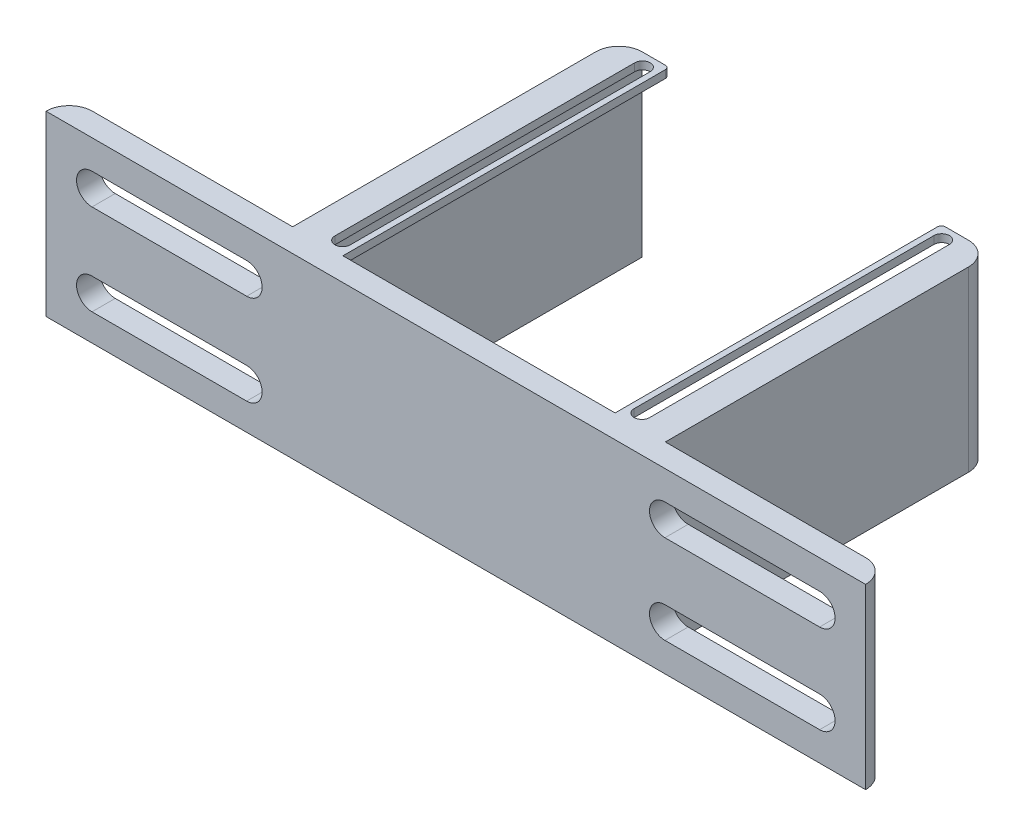
SolidWorks part; units mm, degrees
ref_plane "Front Plane" through (0, 0, 0) normal (0, 0, 1) x (1, 0, 0)
ref_plane "Top Plane" through (0, 0, 0) normal (0, 1, 0) x (1, 0, 0)
ref_plane "Right Plane" through (0, 0, 0) normal (1, 0, 0) x (0, 0, -1)
sketch "Sketch1" plane through (0, 0, 0) normal (0, 1, 0) x (1, 0, 0)
  line L0 (-53, 0) -> (53, 0)
  line L1 (53, 0) -> (53, 3)
  line L2 (53, 3) -> (24.1, 3)
  line L3 (24.1, 3) -> (24.1, 45.2)
  line L4 (24.1, 45.2) -> (21.1, 45.2)
  line L5 (21.1, 45.2) -> (21.1, 3)
  line L6 (21.1, 3) -> (-21.1, 3)
  line L7 (0, 0) -> (0, 100) construction
  line L9 (-53, 0) -> (-53, 3)
  line L10 (21.1, 3) -> (18.1, 3)
  line L11 (21.1, 3) -> (21.1, 45.2)
  line L12 (21.1, 45.2) -> (18.1, 45.2)
  line L13 (18.1, 3) -> (18.1, 45.2)
  line L14 (-53, 3) -> (-24.1, 3)
  line L15 (-24.1, 3) -> (-24.1, 45.2)
  line L16 (-24.1, 45.2) -> (-21.1, 45.2)
  line L17 (-21.1, 45.2) -> (-18.1, 45.2)
  line L18 (-21.1, 45.2) -> (-21.1, 3)
  line L19 (-18.1, 3) -> (-18.1, 45.2)
  point P20 (0, 3)
  dimension "D1" = 28.9
  dimension "D2" = 3
  dimension "D3" = 3
  dimension "D4" = 21.1
  dimension "D5" = 3
  dimension "D6" = 42.2
  dimension "D7" = 3
extrude "Boss-Extrude5" add sketch "Sketch1" along normal blind 23 contours L18 L6 L5 L4 L3 L2 L1 L0 L9 L14 L15 L16
sketch "Sketch3" plane through (0, 0, -3) normal (0, 0, -1) x (-1, 0, 0)
  line L1 (-21.1, 23) -> (-17.6, 23)
  line L2 (-21.1, 23) -> (-21.1, 22)
  line L3 (-21.1, 22) -> (-17.6, 22)
  line L4 (-17.6, 23) -> (-17.6, 22)
  line L5 (21.1, 23) -> (17.6, 23)
  line L6 (21.1, 23) -> (21.1, 22)
  line L7 (21.1, 22) -> (17.6, 22)
  line L8 (17.6, 23) -> (17.6, 22)
  point P10 (-17.6, 22.5)
  dimension "D1" = 1
  dimension "D2" = 3.5
  dimension "D3" = 1
  dimension "D4" = 3.5
extrude "Boss-Extrude7" add sketch "Sketch3" along normal blind 42.2
sketch "Sketch4" plane through (0, 23, 0) normal (0, 1, 0) x (1, 0, 0)
  line L0 (17.6, 45.2) -> (24.1, 45.2) construction
sketch "Sketch5" plane through (0, 22, 0) normal (0, -1, 0) x (-1, 0, 0)
  line L0 (19.35, 45.2) -> (19.35, 3) construction
  line L1 (17.6, 45.2) -> (21.1, 45.2) construction
  line L2 (17.6, 3) -> (21.1, 3) construction
  line L3 (21.1, 24.1) -> (17.6, 24.1) construction
  line L4 (21.1, 45.2) -> (21.1, 3) construction
  line L5 (17.6, 45.2) -> (17.6, 3) construction
  line L6 (-19.35, 3) -> (-19.35, 45.2) construction
  line L7 (-21.1, 3) -> (-17.6, 3) construction
  line L8 (-17.6, 45.2) -> (-24.1, 45.2) construction
  line L9 (-19.35, 45.2) -> (-21.1, 24.1) construction
  line L10 (-21.1, 45.2) -> (-21.1, 3) construction
  line L11 (-19.35, 43.4907) -> (-19.35, 4.7093) construction
  line L12 (-18.35, 43.4907) -> (-18.35, 4.7093)
  line L13 (-20.35, 43.4907) -> (-20.35, 4.7093)
  line L14 (-19.35, 24.1) -> (19.35, 24.1) construction
  line L15 (-19.35, 3.7093) -> (19.35, 3.7093) construction
  line L16 (19.35, 4.7093) -> (19.35, 43.4907) construction
  line L17 (18.35, 4.7093) -> (18.35, 43.4907)
  line L18 (20.35, 4.7093) -> (20.35, 43.4907)
  arc A0 (-18.35, 43.4907) -> (-20.35, 43.4907) centre (-19.35, 43.4907) ccw
  arc A1 (-20.35, 4.7093) -> (-18.35, 4.7093) centre (-19.35, 4.7093) ccw
  arc A2 (18.35, 4.7093) -> (20.35, 4.7093) centre (19.35, 4.7093) ccw
  arc A3 (20.35, 43.4907) -> (18.35, 43.4907) centre (19.35, 43.4907) ccw
  point P23 (-19.35, 24.1)
  point P34 (19.35, 24.1)
extrude "Cut-Extrude3" cut sketch "Sketch5" against normal blind 42.2 contours L12 A1 L13 A0
extrude "Cut-Extrude4" cut sketch "Sketch5<4>" against normal blind 42.2 contours L18 A3 L17 A2
sketch "Sketch5<4>" plane through (0, 22, 0) normal (0, -1, 0) x (-1, 0, 0) same geometry as "Sketch5"
fillet "Fillet1" radius 3 1 edges at (-24.1, 11.5, -45.2)
fillet "Fillet2" radius 3 1 edges at (24.1, 11.5, -45.2)
fillet "Fillet3" radius 0.5 1 edges at (-17.6, 22.5, -45.2)
fillet "Fillet4" radius 0.5 1 edges at (17.6, 22.5, -45.2)
fillet "Fillet5" radius 3 1 edges at (53, 11.5, -3)
fillet "Fillet6" radius 3 1 edges at (-53, 11.5, -3)
sketch "Sketch6" plane through (0, 0, -3) normal (0, 0, -1) x (-1, 0, 0)
  line L0 (-50, 11.5) -> (-24.1, 11.5) construction
  line L1 (-50, 23) -> (-50, 0) construction
  line L2 (-24.1, 23) -> (-24.1, 0) construction
  line L3 (-24.1, 11.5) -> (-37.05, 11.5) construction
  line L4 (-37.05, 11.5) -> (-37.05, 23) construction
  line L5 (-50, 23) -> (-24.1, 23) construction
  line L6 (-37.05, 11.5) -> (-37.05, 0) construction
  line L7 (-50, 0) -> (-24.1, 0) construction
  line L8 (-37.05, 5.75) -> (-50, 5.75) construction
  line L9 (-50, 5.75) -> (-37.05, 5.75) construction
  line L10 (-37.05, 5.75) -> (-24.1, 5.75) construction
  line L11 (-37.05, 17.25) -> (-50, 17.25) construction
  line L12 (-50, 17.25) -> (-37.05, 17.25) construction
  line L13 (-37.05, 17.25) -> (-24.1, 17.25) construction
  line L14 (-27.05, 17.25) -> (-47.05, 17.25) construction
  line L15 (-27.05, 15.25) -> (-47.05, 15.25)
  line L16 (-27.05, 19.25) -> (-47.05, 19.25)
  line L17 (-27.05, 5.75) -> (-47.05, 5.75) construction
  line L18 (-27.05, 3.75) -> (-47.05, 3.75)
  line L19 (-27.05, 7.75) -> (-47.05, 7.75)
  arc A0 (-27.05, 15.25) -> (-27.05, 19.25) centre (-27.05, 17.25) ccw
  arc A1 (-47.05, 19.25) -> (-47.05, 15.25) centre (-47.05, 17.25) ccw
  arc A2 (-27.05, 3.75) -> (-27.05, 7.75) centre (-27.05, 5.75) ccw
  arc A3 (-47.05, 7.75) -> (-47.05, 3.75) centre (-47.05, 5.75) ccw
  point P21 (-37.05, 17.25)
  point P27 (-37.05, 5.75)
extrude "Cut-Extrude5" cut sketch "Sketch6" against normal blind 42.2
sketch "Sketch7" plane through (0, 0, -3) normal (0, 0, -1) x (-1, 0, 0)
  line L0 (24.1, 11.5) -> (50, 11.5) construction
  line L1 (24.1, 23) -> (24.1, 0) construction
  line L2 (50, 0) -> (50, 23) construction
  line L3 (50, 11.5) -> (50, 23) construction
  line L4 (37.05, 11.5) -> (37.05, 23) construction
  line L5 (50, 23) -> (24.1, 23) construction
  line L6 (37.05, 23) -> (37.05, 0) construction
  line L7 (50, 0) -> (24.1, 0) construction
  line L8 (24.1, 23) -> (24.1, 0) construction
  line L9 (50, 17.25) -> (24.1, 17.25) construction
  line L10 (37.05, 0) -> (37.05, 11.5) construction
  line L11 (37.05, 0) -> (37.05, 11.5) construction
  line L12 (24.1, 0) -> (24.1, 11.5) construction
  line L13 (24.1, 5.503) -> (50, 5.503) construction
  line L14 (27.05, 5.503) -> (47.05, 5.503) construction
  line L15 (27.05, 7.503) -> (47.05, 7.503)
  line L16 (27.05, 3.503) -> (47.05, 3.503)
  line L17 (47.05, 17.25) -> (27.05, 17.25) construction
  line L18 (47.05, 15.25) -> (27.05, 15.25)
  line L19 (47.05, 19.25) -> (27.05, 19.25)
  arc A0 (27.05, 7.503) -> (27.05, 3.503) centre (27.05, 5.503) ccw
  arc A1 (47.05, 3.503) -> (47.05, 7.503) centre (47.05, 5.503) ccw
  arc A2 (47.05, 15.25) -> (47.05, 19.25) centre (47.05, 17.25) ccw
  arc A3 (27.05, 19.25) -> (27.05, 15.25) centre (27.05, 17.25) ccw
  point P25 (37.05, 5.503)
  point P31 (37.05, 17.25)
  point P37 (0, 0)
  point P38 (0, 0)
extrude "Cut-Extrude6" cut sketch "Sketch7" against normal blind 42.2 contours L19 A3 L18 A2
extrude "Cut-Extrude7" cut sketch "Sketch7<3>" against normal blind 42.2 contours L15 A1 L16 A0
sketch "Sketch7<3>" plane through (0, 0, -3) normal (0, 0, -1) x (-1, 0, 0) same geometry as "Sketch7"
